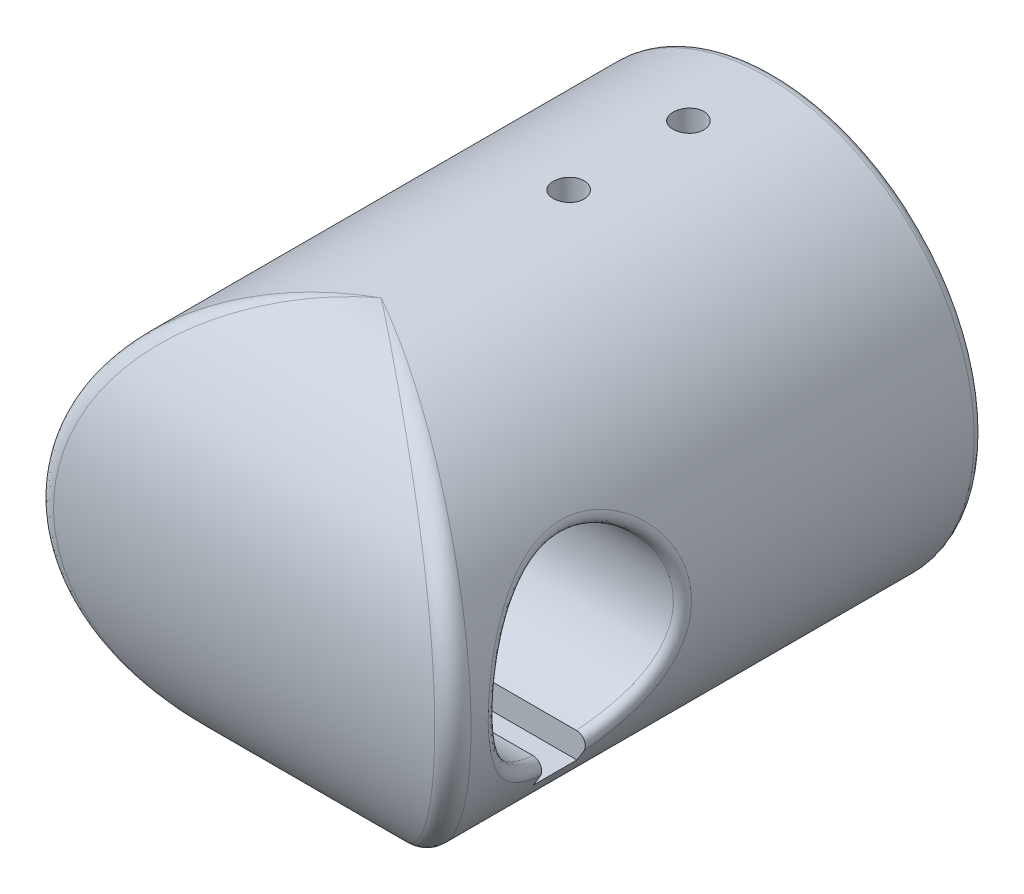
SolidWorks part; units mm, degrees
ref_plane "Front Plane" through (0, 0, 0) normal (1, 0, 0) x (0, 1, 0)
ref_plane "Top Plane" through (0, 0, 0) normal (0, 0, 1) x (0, 1, 0)
ref_plane "Right Plane" through (0, 0, 0) normal (0, 1, 0) x (-1, 0, 0)
sketch "Sketch1" plane through (0, 0, 0) normal (0, 0, 1) x (0, 1, 0)
  circle A0 centre (0, 0) radius 17
  circle A1 centre (0, 0) radius 23
  dimension "D1" = 34
  dimension "D2" = 6
extrude "Boss-Extrude1" add sketch "Sketch1" along normal blind 30
sketch "Sketch2" plane through (0, 0, 0) normal (1, 0, 0) x (0, 1, 0)
  line L0 (23, 0) -> (23, 30) construction
  line L1 (-23, 30) -> (23, 30)
  line L2 (-23, 30) -> (-23, 55)
  line L3 (-23, 55) -> (23, 55)
  line L4 (23, 30) -> (23, 55)
  line L5 (0, 43.3463) -> (23, 43.3463) construction
  line L6 (-12.7136, 45.7463) -> (-9.9136, 45.7463)
  line L7 (-12.7136, 45.7463) -> (-12.7136, 40.9463)
  line L8 (-12.7136, 40.9463) -> (-9.9136, 40.9463)
  arc A0 (-9.9136, 40.9463) -> (-9.9136, 45.7463) centre (0, 43.3463) ccw
  point P9 (-10.2, 43.3463)
  dimension "D2" = 20.4
  dimension "D1" = 25
  dimension "D3" = 4.8
  dimension "D4" = 23
  dimension "D5" = 2.8
extrude "Boss-Extrude2" add sketch "Sketch2" along normal blind 30 and the other way blind 30
sketch "Sketch5" plane through (0, 0, 30) normal (0, 0, -1) x (1, 0, 0)
  circle A0 centre (0, 0) radius 23
extrude "Cut-Extrude-Thin1" cut sketch "Sketch5" against normal blind 30 thin thin type one direction wall 20
sketch "Sketch7" plane through (0, 0, 30) normal (0, 0, -1) x (1, 0, 0)
  circle A0 centre (0, 0) radius 17
extrude "Cut-Extrude2" cut sketch "Sketch7" against normal blind 1.5
sketch "Sketch9" plane through (0, 0, 55) normal (0, 0, 1) x (1, 0, 0)
  circle A0 centre (0, 0) radius 23
extrude "Boss-Extrude3" add sketch "Sketch9" along normal blind 5
sketch "Sketch11" plane through (0, 0, 0) normal (1, 0, 0) x (0, 1, 0)
  line L1 (-23, 60) -> (-23, 0) construction
  line L3 (23, 0) -> (23, 60) construction
  line L4 (-23, 43.3463) -> (-23, 60)
  line L5 (-23, 60) -> (23, 60)
  line L6 (23, 60) -> (23, 43.3463)
  ellipse E0 centre (0, 43.3463) end of major axis (-23, 43.3463) minor radius 15.0896 (23, 43.3463) -> (-23, 43.3463) ccw
extrude "Cut-Extrude3" cut sketch "Sketch11" against normal blind 28 and the other way blind 30
fillet "Fillet4" radius 2 2 edges at (-22.4196, 5.1342, 58.0551) (22.4196, 5.1342, 58.0551)
fillet "Fillet5" radius 1 2 edges at (17, 0, 0) (23, 0, 0)
fillet "Fillet6" radius 1 2 edges at (-20.6303, 10.1682, 44.1514) (20.6303, 10.1682, 42.5412)
sketch "Sketch12" plane through (0, -12.7136, 0) normal (0, 1, 0) x (-1, 0, 0)
  circle A0 centre (0, 9.4908) radius 1.7
  circle A1 centre (0, 22.6929) radius 1.7
  point P4 (0, 22.6929)
  dimension "D1" = 3.4
extrude "Cut-Extrude4" cut sketch "Sketch12" against normal through all and the other way through all
